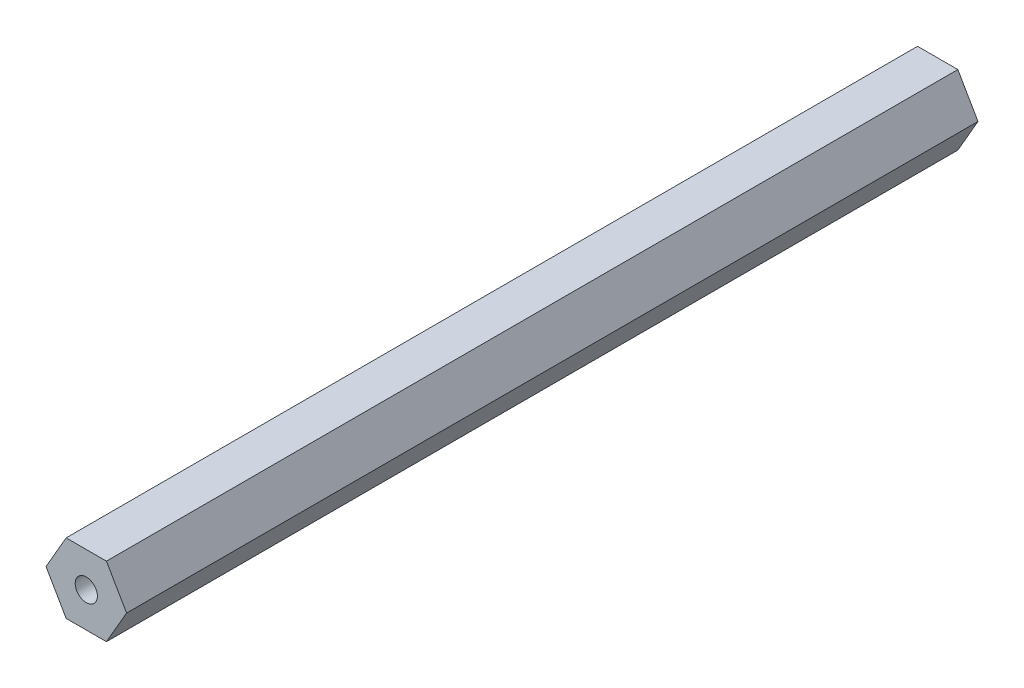
SolidWorks part; units mm, degrees
material "6061-T6 (SS)"
ref_plane "Front" through (0, 0, 0) normal (0, 0, 1) x (1, 0, 0)
ref_plane "Top" through (0, 0, 0) normal (0, 1, 0) x (1, 0, 0)
ref_plane "Right" through (0, 0, 0) normal (1, 0, 0) x (0, 0, -1)
sketch "Sketch1" plane through (0, 0, 0) normal (0, 0, 1) x (1, 0, 0)
  line L1 (7.3323, 0) -> (3.6662, 6.35)
  line L2 (3.6662, 6.35) -> (-3.6662, 6.35)
  line L3 (-3.6662, 6.35) -> (-7.3323, 0)
  line L4 (-7.3323, 0) -> (-3.6662, -6.35)
  line L5 (-3.6662, -6.35) -> (3.6662, -6.35)
  line L6 (3.6662, -6.35) -> (7.3323, 0)
  circle A0 centre (0, 0) radius 6.35 construction
  dimension "D1" = 12.7
extrude "Boss-Extrude1" add sketch "Sketch1" along normal blind 154.94
hole_wizard "#10-32 Tapped Hole1" positions "Sketch2" profile "Sketch4" tap size "#10-32" standard "ANSI Inch"
sketch "Sketch2" plane through (0, 0, 154.94) normal (0, 0, 1) x (1, 0, 0)
  point P0 (0, 0)
sketch "Sketch4" plane through (0, 0, 154.94) normal (1, 0, 0) x (0, -1, 0)
  line L0 (0, 0) -> (0, 77.4133)
  line L1 (0, 77.4133) -> (2.0193, 76.2)
  line L2 (2.0193, 76.2) -> (2.0193, 0)
  line L5 (2.0193, 0) -> (0, 0)
  line L10 (0, 77.4133) -> (-2.0193, 76.2) construction
  line L11 (0, -6.35) -> (0, 107.95) construction
  dimension "Tap Drill Dia." = 4.0386
  dimension "Tap Drill Depth" = 76.2
  dimension "Drill Angle" = 118
cosmetic thread "Hole Thread1" parameters "D1"=9.652, "D2"=4.826
